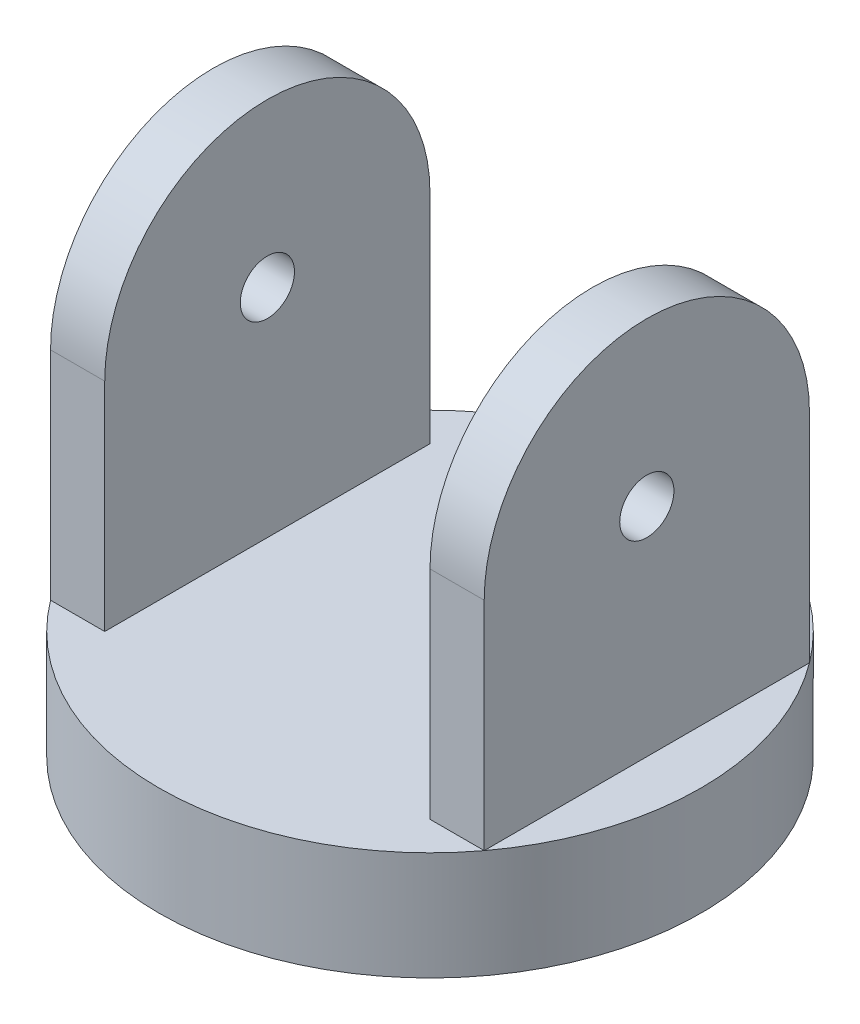
SolidWorks part; units mm, degrees
ref_plane "Front Plane" through (0, 0, 0) normal (0, 0, 1) x (1, 0, 0)
ref_plane "Top Plane" through (0, 0, 0) normal (0, 1, 0) x (1, 0, 0)
ref_plane "Right Plane" through (0, 0, 0) normal (1, 0, 0) x (0, 0, -1)
sketch "Sketch1" plane through (0, 0, 0) normal (0, 1, 0) x (1, 0, 0)
  circle A0 centre (0, 0) radius 25
extrude "Boss-Extrude1" add sketch "Sketch1" along normal blind 10
sketch "Sketch2" plane through (0, 10, 0) normal (0, 1, 0) x (1, 0, 0)
  line L0 (20, -15) -> (15, -15)
  line L1 (20, -15) -> (20, 15)
  line L2 (15, -15) -> (15, 15)
  line L3 (-15, 15) -> (-20, 15)
  line L4 (-15, -15) -> (-20, -15)
  line L5 (-15, -15) -> (-15, 15)
  line L6 (-20, -15) -> (-20, 15)
  line L8 (20, 15) -> (15, 15)
  circle A1 centre (0, 0) radius 25 construction
  dimension "D1" = 30
  dimension "D2" = 40
  dimension "D3" = 15
extrude "Boss-Extrude2" add sketch "Sketch2" along normal blind 40
sketch "Sketch3" plane through (-20, 0, 0) normal (-1, 0, 0) x (0, 0, 1)
  line L0 (-15, 50) -> (-15, 10) construction
  line L1 (15, 50) -> (15, 10) construction
  line L2 (-15, 30) -> (-15, 50)
  line L4 (15, 50) -> (15, 30)
  arc A0 (15, 30) -> (-15, 30) centre (0, 30) ccw
  circle A1 centre (0, 30) radius 2.5
  line M2 (15, 10) -> (15, 50)
  line M3 (15, 50) -> (-15, 50)
  line M4 (-15, 50) -> (-15, 10)
extrude "Cut-Extrude1" cut sketch "Sketch3" against normal through all contours A0 M2 M3 M4 | A1 region at (-20, 45.2086, 0) region at (-20, 30, 0)
